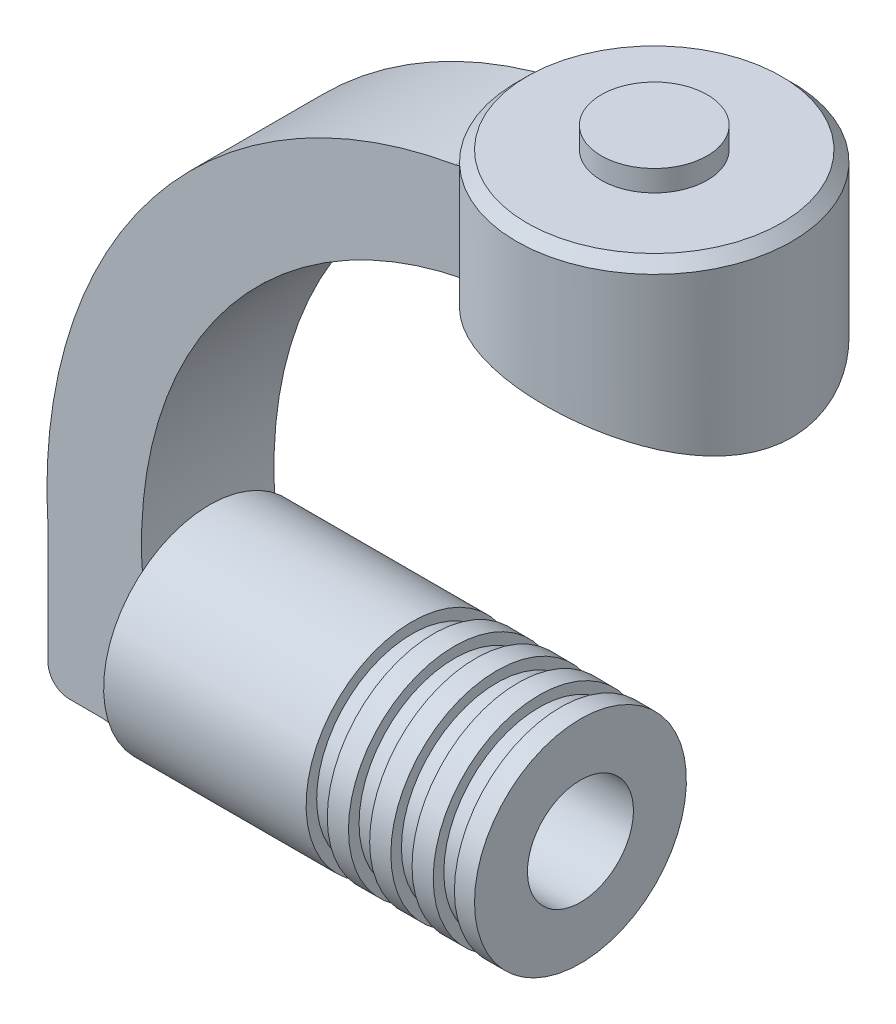
SolidWorks part; units mm, degrees
ref_plane "Ön Düzlem" through (0, 0, 0) normal (0, 0, 1) x (1, 0, 0)
ref_plane "Üst Düzlem" through (0, 0, 0) normal (0, 1, 0) x (1, 0, 0)
ref_plane "Sağ Düzlem" through (0, 0, 0) normal (1, 0, 0) x (0, 0, -1)
sketch "Sketch1" plane through (0, 0, 0) normal (0, 0, 1) x (1, 0, 0)
  line L0 (-90, 0) -> (0, 0) construction
  line L1 (0, 0) -> (0, 120) construction
  line L2 (-90, 12.5) -> (-90, -12.5)
  line L3 (-90, -12.5) -> (-108, -12.5)
  line L4 (-108, -12.5) -> (-108, 13.6093)
  line L5 (0, 120) -> (-26, 120) construction
  line L6 (-26, 120) -> (-26, 94) construction
  line L7 (-26, 94) -> (-31.068, 111.2718)
  arc A0 (-90, 12.5) -> (-26, 94) centre (-15.3304, 19.7426) cw
  arc A1 (-108, 13.6093) -> (-31.068, 111.2718) centre (-15.3304, 19.7426) cw
  arc A2 (-31.068, 111.2718) -> (-26, 112) centre (-15.3304, 19.7426) cw construction
  point P6 (-90, 0)
  dimension "D5" = 75.02
  dimension "D1" = 90
  dimension "D2" = 120
  dimension "D3" = 18
  dimension "D4" = 25
  dimension "D6" = 26
  dimension "D7" = 8
  dimension "D8" = 18
  dimension "D9" = 18
extrude "Boss-Extrude1" add sketch "Sketch1" along normal blind 25
sketch "Sketch3" plane through (-90, 0, 0) normal (1, 0, 0) x (0, 0, -1)
  line L0 (-25, 0) -> (0, 0) construction
  line L1 (-25, -12.5) -> (-25, 12.5) construction
  circle A0 centre (-12.5, 0) radius 20
  dimension "D1" = 40
extrude "Boss-Extrude2" add sketch "Sketch3" along normal blind 70 contours A0
fillet "Fillet1" radius 10 1 edges at (-90, -12.5, 12.5)
fillet "Fillet2" radius 4 1 edges at (-108, -12.5, 12.5)
sketch "Sketch4" plane through (-20, 0, 0) normal (1, 0, 0) x (0, 0, -1)
  circle A0 centre (-12.5, 0) radius 10
  dimension "D1" = 20
extrude "Cut-Extrude1" cut sketch "Sketch4" against normal blind 20
sketch "Sketch5" plane through (0, 0, 0) normal (0, 0, 1) x (1, 0, 0)
  line L0 (0, 0) -> (-90, 0) construction
  line L1 (-90, -15.6125) -> (-90, 12.5) construction
  line L2 (0, 0) -> (0, 120) construction
  dimension "D1" = 120
ref_plane "Plane1" through (0, 120, 0) normal (0, 1, 0) x (1, 0, 0)
sketch "Sketch6" plane through (0, 120, 0) normal (0, 1, 0) x (1, 0, 0)
  line L0 (-31.068, -12.5) -> (18.932, -12.5) construction
  line L1 (-31.068, -25) -> (-31.068, 0) construction
  circle A0 centre (-6.068, -12.5) radius 26
  dimension "D2" = 52
  dimension "D1" = 50
extrude "Boss-Extrude3" add sketch "Sketch6" against normal up to surface (25.8114 mm away) up to face at (-66.1663, 59.6628, 12.5)
sketch "Sketch7" plane through (1.4565, 0.4274, 0) normal (0.9595, 0.2816, 0) x (0, 0, -1)
  line L2 (-25, 115.5177) -> (-25, 107.6969)
  line L3 (-19.6414, 115.5177) -> (-25, 115.5177)
  line L4 (-25, 115.5177) -> (-25, 107.6969)
  line L5 (-19.6414, 115.5177) -> (-25, 115.5177)
  ellipse E1 centre (-12.5, 26.7249) end of major axis (-12.5, 119.0694) minor radius 26 (-19.6414, 115.5177) -> (-25, 107.6969) ccw
  ellipse E2 centre (-12.5, 26.7249) end of major axis (-12.5, 119.0694) minor radius 26 (-19.6414, 115.5177) -> (-25, 107.6969) ccw
  dimension "D1" = 0
extrude "Boss-Extrude4" add sketch "Sketch7" along normal up to surface up to face at (-6.068, 120, 38.5)
sketch "Sketch8" plane through (1.4565, 0.4274, 0) normal (0.9595, 0.2816, 0) x (0, 0, -1)
  line L2 (0, 115.5177) -> (-5.3586, 115.5177)
  line L3 (0, 107.6969) -> (0, 115.5177)
  line L4 (0, 115.5177) -> (-5.3586, 115.5177)
  line L5 (0, 107.6969) -> (0, 115.5177)
  ellipse E1 centre (-12.5, 26.7249) end of major axis (-12.5, 119.0694) minor radius 26 (0, 107.6969) -> (-5.3586, 115.5177) ccw
  ellipse E2 centre (-12.5, 26.7249) end of major axis (-12.5, 119.0694) minor radius 26 (0, 107.6969) -> (-5.3586, 115.5177) ccw
  dimension "D1" = 0
extrude "Boss-Extrude5" add sketch "Sketch8" along normal up to surface up to face at (-6.068, 120, 38.5)
sketch "Sketch9" plane through (0, 120, 0) normal (0, 1, 0) x (1, 0, 0)
  circle A0 centre (-6.068, -12.5) radius 10
  dimension "D1" = 20
extrude "Boss-Extrude6" add sketch "Sketch9" along normal blind 4
chamfer "Chamfer1" distance 2 angle 45 1 edges at (-6.068, 120, 38.5)
sketch "Sketch11" plane through (0, 0, 0) normal (0, 1, 0) x (1, 0, 0)
  line L0 (-20, 7.5) -> (-90, 7.5) construction
  line L1 (-23.79, 9.5) -> (-27.79, 9.5)
  line L2 (-23.79, 9.5) -> (-23.79, 5.5)
  line L3 (-23.79, 5.5) -> (-27.79, 5.5)
  line L4 (-27.79, 9.5) -> (-27.79, 5.5)
  line L5 (-23.79, 9.5) -> (-27.79, 5.5) construction
  line L6 (-23.79, 5.5) -> (-27.79, 9.5) construction
  line L7 (-90, -12.5) -> (-20, -12.5) construction
  line L8 (-31.79, 9.5) -> (-35.79, 9.5)
  line L9 (-31.79, 9.5) -> (-31.79, 5.5)
  line L10 (-31.79, 5.5) -> (-35.79, 5.5)
  line L11 (-35.79, 9.5) -> (-35.79, 5.5)
  line L12 (-31.79, 9.5) -> (-35.79, 5.5) construction
  line L13 (-31.79, 5.5) -> (-35.79, 9.5) construction
  line L14 (-39.79, 9.5) -> (-43.79, 9.5)
  line L15 (-39.79, 9.5) -> (-39.79, 5.5)
  line L16 (-39.79, 5.5) -> (-43.79, 5.5)
  line L17 (-43.79, 9.5) -> (-43.79, 5.5)
  line L18 (-39.79, 9.5) -> (-43.79, 5.5) construction
  line L19 (-39.79, 5.5) -> (-43.79, 9.5) construction
  line L20 (-47.79, 9.5) -> (-51.79, 9.5)
  line L21 (-47.79, 9.5) -> (-47.79, 5.5)
  line L22 (-47.79, 5.5) -> (-51.79, 5.5)
  line L23 (-51.79, 9.5) -> (-51.79, 5.5)
  line L24 (-47.79, 9.5) -> (-51.79, 5.5) construction
  line L25 (-47.79, 5.5) -> (-51.79, 9.5) construction
  line L26 (-90, -25) -> (-90, 0) construction
  line L27 (-20, 7.5) -> (-20, -12.5) construction
  point P0 (-25.79, 7.5)
  point P7 (-33.79, 7.5)
  point P12 (-41.79, 7.5)
  point P17 (-49.79, 7.5)
  point P27 (-20.4242, -12.5)
  dimension "D1" = 4
  dimension "D2" = 4
  dimension "D3" = 4
  dimension "D4" = 4
  dimension "D5" = 4
  dimension "D6" = 4
  dimension "D7" = 4
  dimension "D8" = 4
  dimension "D9" = 3.79
revolve "Cut-Revolve1" cut sketch "Sketch11" angle 360 about L7
